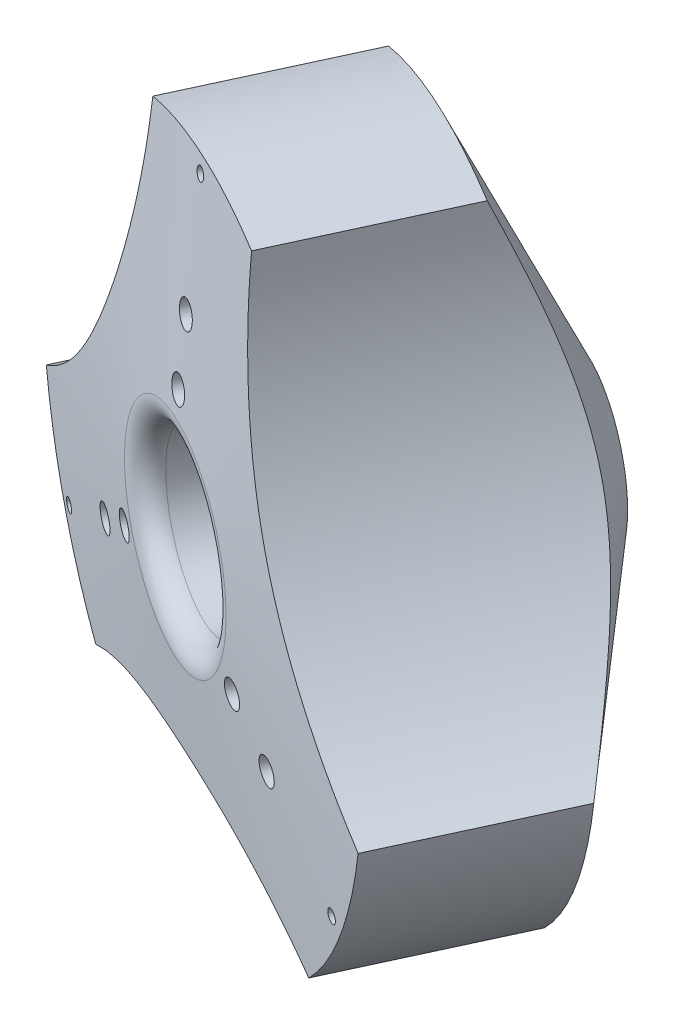
SolidWorks part; units mm, degrees
material "ABS"
ref_plane "前视基准面" through (0, 0, 0) normal (0, 0, 1) x (1, 0, 0)
ref_plane "上视基准面" through (0, 0, 0) normal (0, 1, 0) x (1, 0, 0)
ref_plane "右视基准面" through (0, 0, 0) normal (1, 0, 0) x (0, 0, -1)
other "Configuration Table"
sketch "草图1" plane through (0, 0, 0) normal (0, 1, 0) x (1, 0, 0)
  line L0 (0, 0) -> (50000, 0) construction
  line L1 (0, 0) -> (43301.2702, 25000) construction
  line L2 (0, 0) -> (25000, 43301.2702) construction
  line L3 (0, 0) -> (0, 50000) construction
  line L4 (0, 0) -> (-25000, 43301.2702) construction
  line L5 (0, 0) -> (-43301.2702, 25000) construction
  line L6 (88.4526, -51.0682) -> (112.0193, 0)
  line L7 (55.6014, 0) -> (112.0193, 0)
  line L8 (43.904, -25.348) -> (88.4526, -51.0682)
  line L9 (43.904, -25.348) -> (55.6014, 0)
  line L10 (96.9558, -32.642) -> (87.876, -28.4519) construction
  line L11 (87.876, -28.4519) -> (79.7562, -46.0473)
  line L12 (87.876, -28.4519) -> (101.0059, 0)
  spline S0 degree 4 poles (4.5441, -13.9852) (5.069, -13.9115) (6.1117, -13.7144) (7.5966, -13.2868) (9.4525, -12.4738) (11.1485, -11.4611) (12.673, -10.2854) (14.0902, -8.9027) (15.2006, -7.528) (16.0517, -6.2294) (16.6357, -5.1571) (16.9969, -4.4036) (17.2795, -3.7437) (17.4701, -3.2541) (17.647, -2.7595) (17.7869, -2.3315) (17.8956, -1.9726) (17.9965, -1.6106) (18.0724, -1.3201) (18.1431, -1.0312) (18.201, -0.7763) (18.2495, -0.5466) (18.2961, -0.3139) (18.338, -0.0934) (18.3688, 0.0809) (18.404, 0.2961) (18.438, 0.517) (18.4698, 0.7375) (18.5019, 0.9839) (18.5336, 1.2626) (18.5616, 1.5443) (18.5855, 1.8273) (18.6051, 2.1103) (18.6204, 2.3933) (18.6344, 2.7473) (18.6427, 3.1726) (18.6402, 3.6687) (18.606, 4.6606) (18.4743, 6.0736) (18.1443, 7.891) (17.4882, 10.0676) (16.5951, 12.1579) (15.4804, 14.1385) (14.1536, 15.9992) (12.6297, 17.7192) (10.7951, 19.3989) (8.6272, 20.9716) (6.1287, 22.3558) (3.3088, 23.4722) (0.3713, 24.2251) (-2.6362, 24.611) (-5.6679, 24.6319) (-8.6804, 24.2953) (-11.6337, 23.6131) (-14.4905, 22.6011) (-17.8988, 20.9477) (-21.6682, 18.3857) (-25.4815, 14.66) (-28.8831, 9.6089) (-31.2279, 3.9916) (-32.5355, -2.3024) (-32.5832, -9.4982) (-30.886, -17.2942) (-27.0418, -25.1548) (-21.1423, -32.1629) (-13.78, -37.6027) (-5.394, -41.2569) (3.5764, -43.0207) (12.7127, -42.8868) (21.6333, -40.9289) (30.0036, -37.2857) (37.5425, -32.1439) (44.0239, -25.7248) (49.277, -18.2707) (53.1837, -10.0336) (55.6748, -1.2666) (56.7255, 7.7843) (56.3496, 16.8863) (54.5948, 25.8236) (51.5367, 34.4007) (47.2736, 42.4454) (41.6252, 50.2164) (33.2939, 58.6988) (21.6024, 66.7973) (6.2316, 72.9489) (-11.9297, 75.3897) (-30.1426, 73.5037) (-47.4501, 67.5662) (-63.0493, 58.0235) (-76.3038, 45.4399) (-86.7456, 30.4509) (-94.067, 13.7235) (-98.1075, -4.0757) (-98.837, -22.3066) (-96.337, -40.374) (-90.7813, -57.7411) (-82.4178, -73.9383) (-71.5503, -88.568) (-58.5225, -101.306) (-43.7037, -111.9004) (-27.476, -120.169) (-10.2235, -125.9948) (7.6766, -129.3207) (25.8616, -130.1437) (43.989, -128.5088) (59.522, -125.003) (72.4202, -120.5917) (82.8104, -116.0253) (90.8771, -111.8583) (98.6697, -107.1992) (106.1617, -102.071) (114.2246, -95.801) (122.6763, -88.2215) (131.2888, -79.1727) (139.0767, -69.4058) (144.8157, -60.9536) (149.48, -53.1674) (153.2371, -46.1706) (156.1751, -40.0285) (158.8259, -33.7588) (160.8418, -28.4575) (162.3378, -24.1741) (163.5443, -20.3917) (164.5049, -17.1274) (165.2564, -14.393) (165.828, -12.1982) (166.3703, -9.9944) (166.8184, -8.0627) (167.1848, -6.398) (167.4765, -5.0161) (167.7053, -3.8925) (167.892, -2.9476) (168.0629, -2.0497) (168.1956, -1.3461) (168.4043, -0.1916) (168.4882, 0.2863) (168.6688, 1.3366) (168.7622, 1.9047) (168.8711, 2.5704) (169.0198, 3.5044) (169.1948, 4.6573) (169.389, 6.0027) (169.5701, 7.3351) (169.7422, 8.6768) (169.9433, 10.3507) (170.1641, 12.3645) (170.391, 14.7154) (170.6086, 17.4069) (170.7844, 20.1009) (170.9186, 22.7976) (171.0111, 25.4959) (171.0621, 28.1953) (171.0718, 30.8952) (171.0401, 33.595) (170.9491, 36.9686) (170.6302, 43.7113) (169.6923, 53.7988) (167.722, 65.8035) (165.138, 76.2991) (163.208, 82.7681) (162.3863, 85.3399) knots 0 0 0 0 0 0.002183 0.004365 0.006343 0.00832 0.010298 0.012275 0.014479 0.01558 0.016682 0.0173 0.017918 0.018536 0.018845 0.019463 0.019772 0.020081 0.02039 0.020699 0.021008 0.021162 0.021317 0.021626 0.021918 0.022064 0.02221 0.022501 0.022793 0.023085 0.023377 0.023669 0.023961 0.024253 0.024544 0.025128 0.025712 0.026296 0.028631 0.030966 0.033302 0.035637 0.037972 0.040307 0.042695 0.045083 0.048197 0.05131 0.054424 0.057538 0.060652 0.063766 0.066879 0.069993 0.073107 0.07622 0.082448 0.088676 0.094903 0.10113 0.107357 0.114993 0.124334 0.133675 0.143016 0.152357 0.161699 0.17104 0.18038 0.189722 0.199063 0.208404 0.217745 0.227086 0.236427 0.245769 0.25511 0.264451 0.273792 0.283133 0.292474 0.301815 0.313225 0.331907 0.35059 0.369272 0.387954 0.406636 0.425318 0.444001 0.462683 0.481365 0.500047 0.518729 0.537412 0.556094 0.574776 0.593458 0.612141 0.630823 0.649505 0.668187 0.68687 0.705552 0.724234 0.742916 0.752258 0.761599 0.77094 0.780281 0.789622 0.798963 0.812975 0.826987 0.840998 0.85034 0.85501 0.864351 0.873692 0.878363 0.883033 0.887704 0.892374 0.89471 0.897045 0.89938 0.901716 0.904051 0.905219 0.906387 0.907554 0.908722 0.909306 0.90989 0.911057 0.912447 0.912794 0.913142 0.913837 0.915226 0.916616 0.918006 0.919396 0.920785 0.922175 0.924955 0.927734 0.930513 0.933293 0.936072 0.938852 0.941631 0.944411 0.94719 0.94997 0.955529 0.972205 0.988882 1 1 1 1 1 construction
  spline S1 degree 4 poles (18.3541, 0) (18.3651, 0.0621) (18.381, 0.1554) (18.404, 0.2961) (18.438, 0.517) (18.4698, 0.7375) (18.5019, 0.9839) (18.5336, 1.2626) (18.5616, 1.5443) (18.5855, 1.8273) (18.6051, 2.1103) (18.6204, 2.3933) (18.6344, 2.7473) (18.6427, 3.1726) (18.6402, 3.6687) (18.606, 4.6606) (18.4743, 6.0736) (18.1443, 7.891) (17.4882, 10.0676) (16.5951, 12.1579) (15.4804, 14.1385) (14.1536, 15.9992) (12.6297, 17.7192) (10.7951, 19.3989) (8.6272, 20.9716) (6.1287, 22.3558) (3.3088, 23.4722) (0.3713, 24.2251) (-2.6362, 24.611) (-5.6679, 24.6319) (-8.6804, 24.2953) (-11.6337, 23.6131) (-14.4905, 22.6011) (-17.8988, 20.9477) (-21.6682, 18.3857) (-25.4815, 14.66) (-28.8831, 9.6089) (-31.2279, 3.9916) (-32.5355, -2.3024) (-32.5832, -9.4982) (-30.886, -17.2942) (-27.0418, -25.1548) (-21.1423, -32.1629) (-13.78, -37.6027) (-5.394, -41.2569) (3.5764, -43.0207) (12.7127, -42.8868) (21.6333, -40.9289) (30.0036, -37.2857) (37.5425, -32.1439) (44.0239, -25.7248) (49.277, -18.2707) (53.1837, -10.0336) (55.6748, -1.2666) (56.7255, 7.7843) (56.3496, 16.8863) (54.5948, 25.8236) (51.5367, 34.4007) (47.2736, 42.4454) (41.6252, 50.2164) (33.2939, 58.6988) (21.6024, 66.7973) (6.2316, 72.9489) (-11.9297, 75.3897) (-30.1426, 73.5037) (-47.4501, 67.5662) (-63.0493, 58.0235) (-76.3038, 45.4399) (-86.7456, 30.4509) (-94.067, 13.7235) (-98.1075, -4.0757) (-98.837, -22.3066) (-96.337, -40.374) (-90.7813, -57.7411) (-82.4178, -73.9383) (-71.5503, -88.568) (-58.5225, -101.306) (-43.7037, -111.9004) (-27.476, -120.169) (-10.2235, -125.9948) (7.6766, -129.3207) (25.8616, -130.1437) (43.989, -128.5088) (59.522, -125.003) (72.4202, -120.5917) (82.8104, -116.0253) (90.8771, -111.8583) (98.6697, -107.1992) (106.1617, -102.071) (114.2246, -95.801) (122.6763, -88.2215) (131.2888, -79.1727) (139.0767, -69.4058) (144.8157, -60.9536) (149.48, -53.1674) (153.2371, -46.1706) (156.1751, -40.0285) (158.8259, -33.7588) (160.8418, -28.4575) (162.3378, -24.1741) (163.5443, -20.3917) (164.5049, -17.1274) (165.2564, -14.393) (165.828, -12.1982) (166.3703, -9.9944) (166.8184, -8.0627) (167.1848, -6.398) (167.4765, -5.0161) (167.7053, -3.8925) (167.892, -2.9476) (168.0629, -2.0497) (168.1956, -1.3461) (168.3264, -0.6223) (168.3933, -0.2484) (168.4372, 0) knots 0.021626 0.021626 0.021626 0.021626 0.021626 0.021918 0.022064 0.02221 0.022501 0.022793 0.023085 0.023377 0.023669 0.023961 0.024253 0.024544 0.025128 0.025712 0.026296 0.028631 0.030966 0.033302 0.035637 0.037972 0.040307 0.042695 0.045083 0.048197 0.05131 0.054424 0.057538 0.060652 0.063766 0.066879 0.069993 0.073107 0.07622 0.082448 0.088676 0.094903 0.10113 0.107357 0.114993 0.124334 0.133675 0.143016 0.152357 0.161699 0.17104 0.18038 0.189722 0.199063 0.208404 0.217745 0.227086 0.236427 0.245769 0.25511 0.264451 0.273792 0.283133 0.292474 0.301815 0.313225 0.331907 0.35059 0.369272 0.387954 0.406636 0.425318 0.444001 0.462683 0.481365 0.500047 0.518729 0.537412 0.556094 0.574776 0.593458 0.612141 0.630823 0.649505 0.668187 0.68687 0.705552 0.724234 0.742916 0.752258 0.761599 0.77094 0.780281 0.789622 0.798963 0.812975 0.826987 0.840998 0.85034 0.85501 0.864351 0.873692 0.878363 0.883033 0.887704 0.892374 0.89471 0.897045 0.89938 0.901716 0.904051 0.905219 0.906387 0.907554 0.908722 0.909306 0.90989 0.911057 0.911057 0.911057 0.911057 0.911057
  spline S2 degree 4 poles (26.7771, -19.4547) (27.2791, -18.9699) (28.2564, -17.9726) (29.6389, -16.3972) (31.5138, -13.8737) (32.9647, -11.4834) (34.0651, -9.2997) (34.8847, -7.3726) (35.3191, -6.2309) (35.6599, -5.2409) (35.9229, -4.4091) (36.0959, -3.8235) (36.2363, -3.3192) (36.3702, -2.8132) (36.4765, -2.3905) (36.5777, -1.9654) (36.6735, -1.5395) (36.7371, -1.2443) (36.7899, -0.9895) (36.8338, -0.7701) (36.8689, -0.5895) (36.9122, -0.3614) (36.9643, -0.079) (37.0022, 0.137) (37.056, 0.4587) (37.1012, 0.7414) (37.1347, 0.96) (37.1737, 1.2255) (37.2176, 1.5413) (37.2661, 1.9157) (37.3168, 2.3441) (37.3624, 2.7721) (37.4134, 3.3079) (37.4649, 3.9519) (37.524, 4.9191) (37.5642, 6.2107) (37.5499, 8.58) (37.2749, 12.0191) (36.4953, 16.2666) (34.9181, 21.2024) (32.7382, 25.9024) (30.2297, 29.9345) (27.5748, 33.3344) (24.3272, 36.7897) (20.4102, 40.1789) (15.3713, 43.5302) (9.113, 46.471) (2.4988, 48.4837) (-3.4771, 49.4179) (-8.6498, 49.6296) (-15.5372, 49.2939) (-22.3494, 48.0444) (-29.7217, 45.4984) (-37.3047, 41.3681) (-42.9225, 37.3494) (-49.2948, 31.5248) (-55.7813, 23.4083) (-61.4472, 12.6507) (-65.4181, -1.9048) (-66.0143, -20.496) (-61.2011, -38.6277) (-51.6663, -54.6681) (-39.5267, -67.0168) (-28.241, -75.0457) (-15.7631, -81.0448) (-2.4709, -84.9081) (11.2641, -86.5959) (25.0917, -86.1269) (38.6859, -83.5703) (51.7521, -79.0376) (62.4941, -73.4702) (71.0671, -67.6624) (77.7289, -62.1925) (82.7475, -57.4634) (87.4361, -52.4071) (91.7776, -47.05) (95.7571, -41.4188) (99.3618, -35.5409) (102.1786, -30.2056) (104.3465, -25.5122) (105.8226, -21.9278) (106.7439, -19.5134) (107.4694, -17.486) (108.0246, -15.8552) (108.5543, -14.216) (109.0585, -12.5687) (109.5372, -10.914) (109.9904, -9.2519) (110.418, -7.5833) (110.7697, -6.1172) (111.0551, -4.8577) (111.2824, -3.8044) (111.4574, -2.9629) (111.6056, -2.2213) (111.7181, -1.6396) (111.7961, -1.2276) (111.8764, -0.7956) (111.9824, -0.2107) (112.0406, 0.1173) (112.149, 0.7476) (112.2197, 1.1704) (112.2736, 1.499) (112.3401, 1.912) (112.4454, 2.5814) (112.5829, 3.4978) (112.7468, 4.6683) (112.9181, 6.007) (113.1127, 7.6834) (113.3147, 9.6981) (113.5046, 12.0531) (113.6588, 14.7487) (113.7504, 17.4473) (113.7796, 20.1472) (113.7303, 24.197) (113.4243, 30.2662) (112.8255, 35.6383) (112.057, 40.3021) (111.5392, 42.9519) knots 0 0 0 0 0 0.005611 0.011222 0.016833 0.02525 0.028055 0.030861 0.033666 0.035069 0.036472 0.037875 0.038576 0.039277 0.04068 0.041381 0.042083 0.042784 0.043135 0.043486 0.043836 0.044187 0.044888 0.045754 0.046187 0.04662 0.047052 0.047485 0.048351 0.049216 0.050082 0.050948 0.051813 0.053545 0.055276 0.058738 0.062201 0.072588 0.082976 0.093363 0.103751 0.114138 0.121063 0.127988 0.141838 0.155688 0.169538 0.183388 0.197238 0.204163 0.211088 0.238788 0.252638 0.266488 0.280339 0.294189 0.321888 0.349589 0.377289 0.414571 0.469971 0.497671 0.525371 0.553071 0.580771 0.608471 0.636171 0.663871 0.691571 0.719271 0.746971 0.760821 0.774671 0.788521 0.802371 0.816222 0.830072 0.843922 0.857772 0.864697 0.871622 0.875084 0.878547 0.882009 0.885472 0.888934 0.892397 0.895859 0.899322 0.902784 0.904515 0.906247 0.907978 0.909709 0.910575 0.911008 0.91144 0.913172 0.914528 0.915207 0.915885 0.916563 0.917242 0.918599 0.921312 0.924025 0.926739 0.929452 0.934879 0.940306 0.945732 0.951159 0.956586 0.962013 0.978293 1 1 1 1 1 construction
  spline S3 degree 4 poles (36.9778, 0) (36.994, 0.0921) (37.0177, 0.2297) (37.056, 0.4587) (37.1012, 0.7414) (37.1347, 0.96) (37.1737, 1.2255) (37.2176, 1.5413) (37.2661, 1.9157) (37.3168, 2.3441) (37.3624, 2.7721) (37.4134, 3.3079) (37.4649, 3.9519) (37.524, 4.9191) (37.5642, 6.2107) (37.5499, 8.58) (37.2749, 12.0191) (36.4953, 16.2666) (34.9181, 21.2024) (32.7382, 25.9024) (30.2297, 29.9345) (27.5748, 33.3344) (24.3272, 36.7897) (20.4102, 40.1789) (15.3713, 43.5302) (9.113, 46.471) (2.4988, 48.4837) (-3.4771, 49.4179) (-8.6498, 49.6296) (-15.5372, 49.2939) (-22.3494, 48.0444) (-29.7217, 45.4984) (-37.3047, 41.3681) (-42.9225, 37.3494) (-49.2948, 31.5248) (-55.7813, 23.4083) (-61.4472, 12.6507) (-65.4181, -1.9048) (-66.0143, -20.496) (-61.2011, -38.6277) (-51.6663, -54.6681) (-39.5267, -67.0168) (-28.241, -75.0457) (-15.7631, -81.0448) (-2.4709, -84.9081) (11.2641, -86.5959) (25.0917, -86.1269) (38.6859, -83.5703) (51.7521, -79.0376) (62.4941, -73.4702) (71.0671, -67.6624) (77.7289, -62.1925) (82.7475, -57.4634) (87.4361, -52.4071) (91.7776, -47.05) (95.7571, -41.4188) (99.3618, -35.5409) (102.1786, -30.2056) (104.3465, -25.5122) (105.8226, -21.9278) (106.7439, -19.5134) (107.4694, -17.486) (108.0246, -15.8552) (108.5543, -14.216) (109.0585, -12.5687) (109.5372, -10.914) (109.9904, -9.2519) (110.418, -7.5833) (110.7697, -6.1172) (111.0551, -4.8577) (111.2824, -3.8044) (111.4574, -2.9629) (111.6056, -2.2213) (111.7181, -1.6396) (111.7961, -1.2276) (111.8764, -0.7956) (111.946, -0.4114) (111.9868, -0.1841) (112.0193, 0) knots 0.044888 0.044888 0.044888 0.044888 0.044888 0.045754 0.046187 0.04662 0.047052 0.047485 0.048351 0.049216 0.050082 0.050948 0.051813 0.053545 0.055276 0.058738 0.062201 0.072588 0.082976 0.093363 0.103751 0.114138 0.121063 0.127988 0.141838 0.155688 0.169538 0.183388 0.197238 0.204163 0.211088 0.238788 0.252638 0.266488 0.280339 0.294189 0.321888 0.349589 0.377289 0.414571 0.469971 0.497671 0.525371 0.553071 0.580771 0.608471 0.636171 0.663871 0.691571 0.719271 0.746971 0.760821 0.774671 0.788521 0.802371 0.816222 0.830072 0.843922 0.857772 0.864697 0.871622 0.875084 0.878547 0.882009 0.885472 0.888934 0.892397 0.895859 0.899322 0.902784 0.904515 0.906247 0.907978 0.909709 0.910575 0.911008 0.91144 0.913172 0.913172 0.913172 0.913172 0.913172
  dimension "D1" = 10
revolve "旋转1" add sketch "草图1" angle 360 about L6 region at (72.4978, 0, 18.4641) region at (50.4024, 0, 13.0224)
ref_plane "基准面1" through (-3.5161, 0, 7.6192) normal (-0.419, 0, 0.908) x (0.908, 0, 0.419)
sketch "草图2" plane through (-3.5161, 0, 7.6192) normal (-0.419, 0, 0.908) x (0.908, 0, 0.419)
  line L0 (101.7114, 51.2264) -> (101.7114, 48.7264)
  line L1 (101.7114, 0) -> (101.7114, 20) construction
  line L2 (101.7114, 20) -> (101.7114, 30) construction
  line L4 (101.7114, 0) -> (13.3768, 51) construction
  circle A0 centre (101.7114, 0) radius 51.2264 construction
  circle A1 centre (13.3768, 51) radius 72.5
  circle A2 centre (101.7114, 48.7264) radius 1
  circle A4 centre (101.7114, 30) radius 2
  circle A5 centre (101.7114, 20) radius 2
  circle A6 centre (190.046, 51) radius 72.5
  circle A7 centre (143.9097, -24.3632) radius 1
  circle A9 centre (127.6922, -15) radius 2
  circle A10 centre (119.0319, -10) radius 2
  circle A11 centre (101.7114, -102) radius 72.5
  circle A12 centre (59.5132, -24.3632) radius 1
  circle A14 centre (75.7307, -15) radius 2
  circle A15 centre (84.3909, -10) radius 2
  circle A16 centre (101.7114, 0) radius 12.5
  dimension "D7" = 145
  dimension "D8" = 2
  dimension "D10" = 4
  dimension "D11" = 4
  dimension "D4" = 25
  dimension "D1" = 2.5
  dimension "D2" = 20
  dimension "D3" = 10
  dimension "D5" = 102
  dimension "D6" = 60
  dimension "D12" = 3
extrude "切除-拉伸1" cut sketch "草图2" against normal blind 60 contours A1 | A6 | A11 | A2 | A4 | A5 | A10 | A9 | A7 | A15 | A14 | A12 | A16 region at (8.6299, 51, 13.2243) region at (88.2121, 48.0393, 49.9495) region at (88.836, 30, 50.2374) region at (88.836, 20, 50.2374) region at (169.0422, 51, 87.2505) region at (127.1513, -24.3632, 67.9189) region at (112.4261, -15, 61.1236) region at (104.5627, -10, 57.4948) region at (88.836, -102, 50.2374) region at (50.5208, -24.3632, 32.5559) region at (65.246, -15, 39.3512) region at (73.1093, -10, 42.9799) region at (88.836, 0, 50.2374)
ref_plane "基准面2" through (90.5361, 0, 41.7801) normal (0.908, 0, 0.419) x (0.419, 0, -0.908)
ref_plane "基准面3" through (92.3521, 0, 42.6181) normal (0.908, 0, 0.419) x (0.419, 0, -0.908)
fillet "圆角1" radius 3.5 1 edges at (77.5821, 0, 44.792)
shell "抽壳1" thickness 2
sketch "草图3" plane through (92.3521, 0, 42.6181) normal (0.908, 0, 0.419) x (0.419, 0, -0.908)
  line L1 (-5.315, 23.285) -> (34.2094, 23.285)
  line L2 (-5.315, 23.285) -> (-5.315, 26.1593)
  line L3 (-5.315, 26.1593) -> (34.2094, 26.1593)
  line L4 (34.2094, 23.285) -> (34.2094, 26.1593)
  line L5 (-6.3683, 16.2536) -> (38.8042, 16.2536)
  line L6 (-6.3683, 16.2536) -> (-6.3683, 13.8567)
  line L7 (-6.3683, 13.8567) -> (38.8042, 13.8567)
  line L8 (38.8042, 16.2536) -> (38.8042, 13.8567)
extrude "凸台-拉伸1" add sketch "草图3" along normal mid plane 1
ref_axis "基准轴1" through (106.2553, 0, 12.4904) along (-0.419, 0, 0.908)
pattern_circular "阵列(圆周)1" count 3 over 360 about axis through (106.2553, 0, 12.4904) along (-0.419, 0, 0.908) of "凸台-拉伸1"
